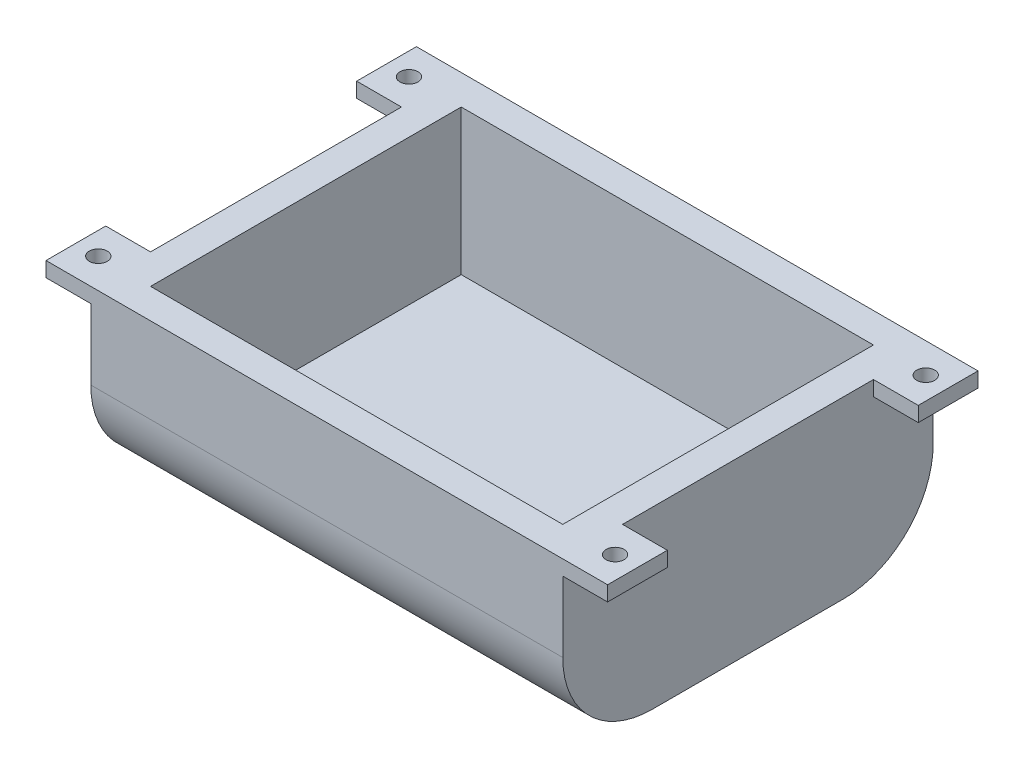
SolidWorks part; units mm, degrees
ref_plane "Front Plane" through (0, 0, 0) normal (0, 0, 1) x (1, 0, 0)
ref_plane "Top Plane" through (0, 0, 0) normal (0, 1, 0) x (1, 0, 0)
ref_plane "Right Plane" through (0, 0, 0) normal (1, 0, 0) x (0, 0, -1)
sketch "Sketch1" plane through (0, 0, 0) normal (0, 1, 0) x (1, 0, 0)
  line L0 (39.5, -31) -> (-39.5, -31)
  line L1 (34.5, -26) -> (-34.5, -26)
  line L2 (34.5, -26) -> (34.5, 26)
  line L3 (34.5, 26) -> (-34.5, 26)
  line L4 (-34.5, -26) -> (-34.5, 26)
  line L5 (34.5, -26) -> (-34.5, 26) construction
  line L6 (34.5, 26) -> (-34.5, -26) construction
  line L7 (-39.5, -31) -> (-39.5, 31)
  line L8 (39.5, 31) -> (-39.5, 31)
  line L9 (39.5, -31) -> (39.5, 31)
  point P0 (0, 0)
  dimension "D1" = 52
  dimension "D2" = 69
  dimension "D3" = 5
extrude "Boss-Extrude1" add sketch "Sketch1" along normal blind 24.3
extrude "Boss-Extrude2" add sketch "Sketch1<2>" against normal blind 5 contours L0 L9 L8 L7 L1 L4 L3 L2 | L4 L1 L2 L3 | L0 L7 L8 L9 region at (0, 0, 29.9958) region at (0, 0, 0)
sketch "Sketch1<2>" plane through (0, 0, 0) normal (0, 1, 0) x (1, 0, 0) same geometry as "Sketch1"
sketch "Sketch3" plane through (-39.5, 0, 0) normal (-1, 0, 0) x (0, 0, 1)
  line L0 (0, 0) -> (0, 24.3) construction
  line L1 (-31, 24.3) -> (-21, 24.3)
  line L2 (-31, 24.3) -> (-31, 21.8)
  line L3 (-31, 21.8) -> (-21, 21.8)
  line L4 (-21, 24.3) -> (-21, 21.8)
  line L5 (-31, 24.3) -> (31, 24.3) construction
  line L6 (31, 21.8) -> (21, 21.8)
  line L7 (21, 24.3) -> (21, 21.8)
  line L8 (31, 24.3) -> (21, 24.3)
  line L9 (31, 24.3) -> (31, 21.8)
  dimension "D1" = 10
  dimension "D2" = 2.5
extrude "Boss-Extrude3" add sketch "Sketch3" along normal blind 7.5
ref_plane "Plane1" through (0, 0, 0) normal (-1, 0, 0) x (0, 0, 1)
mirror "Mirror1" about plane through (0, 0, 0) normal (-1, 0, 0) of "Boss-Extrude3"
sketch "Sketch4" plane through (0, 21.8, 0) normal (0, -1, 0) x (1, 0, 0)
  line L0 (47, 26) -> (39.5, 26) construction
  line L1 (47, 21) -> (47, 31) construction
  line L2 (39.5, 21) -> (39.5, 31) construction
  line L3 (43.25, 31) -> (43.25, 21) construction
  line L4 (47, 31) -> (39.5, 31) construction
  line L5 (47, 21) -> (39.5, 21) construction
  line L6 (0, 0) -> (0, 9.6014) construction
  line L7 (0, 0) -> (-6.5097, 0) construction
  circle A0 centre (43.25, 26) radius 1.5
  circle A1 centre (-43.25, 26) radius 1.5
  circle A2 centre (-43.25, -26) radius 1.5
  circle A3 centre (43.25, -26) radius 1.5
  dimension "D1" = 3
extrude "Cut-Extrude1" cut sketch "Sketch4" against normal through all both and the other way through all
fillet "Fillet1" radius 15 2 edges at (0, -5, -31) (0, -5, 31)
